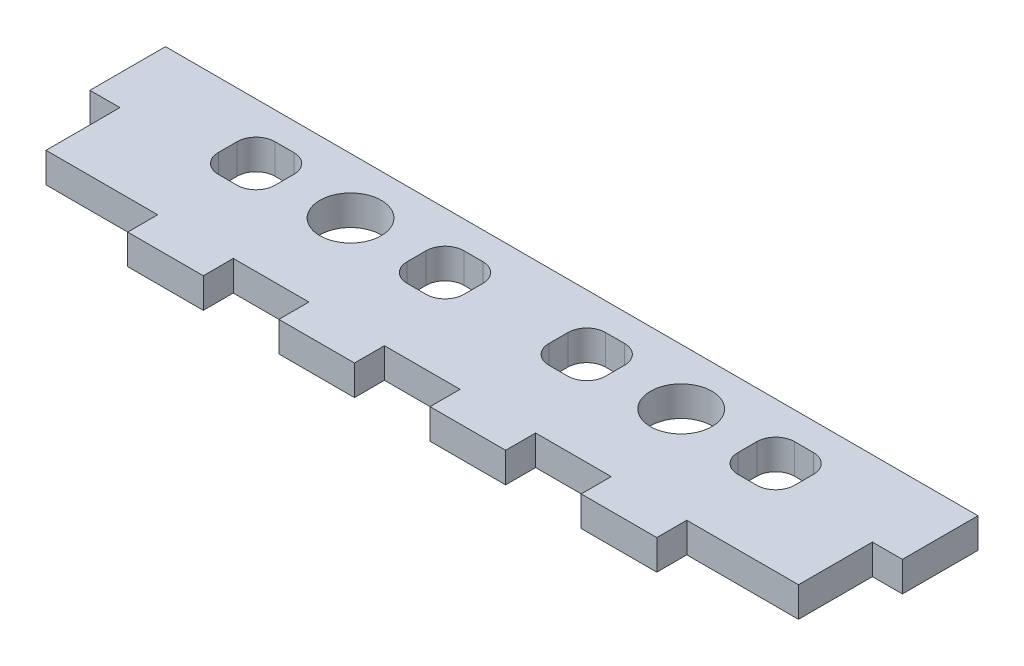
SolidWorks part; units mm, degrees
ref_plane "Front Plane" through (0, 0, 0) normal (0, 0, 1) x (1, 0, 0)
ref_plane "Top Plane" through (0, 0, 0) normal (0, 1, 0) x (1, 0, 0)
ref_plane "Right Plane" through (0, 0, 0) normal (1, 0, 0) x (0, 0, -1)
sketch "Sketch3" plane through (0, 0, 0) normal (0, 1, 0) x (1, 0, 0)
  line L1 (0, 0) -> (86, 0)
  line L2 (0, 0) -> (0, -30)
  line L3 (0, -30) -> (86, -30)
  line L4 (86, 0) -> (86, -30)
  dimension "D1" = 30
  dimension "D2" = 86
extrude "Boss-Extrude1" add sketch "Sketch3" along normal blind 3.175
sketch "Sketch4" plane through (0, 3.175, 0) normal (0, 1, 0) x (1, 0, 0)
  line L0 (43, 0) -> (43, -30) construction
  line L1 (86, 0) -> (0, 0) construction
  line L2 (0, -30) -> (86, -30) construction
  line L3 (0, -15) -> (86, -15) construction
  line L4 (0, 0) -> (0, -30) construction
  line L5 (86, -30) -> (86, 0) construction
  line L6 (15, -30) -> (15, -26.825)
  line L7 (39, -30) -> (47, -30)
  line L8 (0, -26.825) -> (15, -26.825)
  line L9 (39, -26.825) -> (47, -26.825)
  line L10 (47, -30) -> (47, -26.825)
  line L11 (55, -30) -> (63, -30)
  line L12 (55, -30) -> (55, -26.825)
  line L13 (55, -26.825) -> (63, -26.825)
  line L14 (63, -30) -> (63, -26.825)
  line L15 (86, -30) -> (71, -30)
  line L16 (86, -30) -> (86, -26.825)
  line L17 (86, -26.825) -> (71, -26.825)
  line L18 (71, -30) -> (71, -26.825)
  line L19 (0, -30) -> (0, -26.825)
  line L20 (0, -30) -> (15, -30)
  line L21 (23, -30) -> (23, -26.825)
  line L22 (31, -26.825) -> (23, -26.825)
  line L23 (31, -30) -> (31, -26.825)
  line L24 (31, -30) -> (23, -30)
  line L25 (39, -30) -> (39, -26.825)
  line L26 (86, -19) -> (86, -26.825)
  line L27 (0, 0) -> (3.175, 0)
  line L28 (0, 0) -> (0, -11)
  line L29 (0, -11) -> (3.175, -11)
  line L30 (3.175, 0) -> (3.175, -11)
  line L31 (82.825, -19) -> (82.825, -26.825)
  line L32 (86, -19) -> (82.825, -19)
  line L33 (82.825, 0) -> (82.825, -11)
  line L34 (86, -11) -> (82.825, -11)
  line L35 (0, -19) -> (3.175, -19)
  line L36 (0, -19) -> (0, -26.825)
  line L37 (0, -26.825) -> (3.175, -26.825)
  line L38 (3.175, -19) -> (3.175, -26.825)
  line L39 (86, 0) -> (86, -11)
  line L40 (86, 0) -> (82.825, 0)
  line L41 (82.825, -26.825) -> (86, -26.825)
  line L42 (86, -19) -> (86, -26.825)
  point P34 (43, -26.825)
  line M11 (0, 0) -> (0, -30)
  line M12 (0, -30) -> (86, -30)
  line M13 (86, -30) -> (86, 0)
  line M14 (86, 0) -> (0, 0)
  dimension "D1" = 4
  dimension "D2" = 3.175
  dimension "D3" = 8
  dimension "D4" = 3.175
  dimension "D5" = 8
  dimension "D6" = 3.175
  dimension "D7" = 8
  dimension "D8" = 8
extrude "Cut-Extrude1" cut sketch "Sketch4" against normal up to next contours L38 L35 L8 M11 | L8 L6 M11 M12 | L23 L22 L21 M12 | L25 L10 L9 M12 | L14 L13 L12 M12 | L32 L31 L17 M13 | L34 L33 M13 M14 | L18 L17 M12 M13 | L30 L29 M14 M11 | L17 L18 L15 L16 region at (7.5, 3.175, 28.4125) region at (27, 3.175, 28.4125) region at (1.5875, 3.175, 22.9125) region at (43, 3.175, 28.4125) region at (1.5875, 3.175, 5.5) region at (59, 3.175, 28.4125) region at (84.4125, 3.175, 5.5) region at (78.5, 3.175, 28.4125) region at (84.4125, 3.175, 22.9125)
sketch "Sketch5" plane through (0, 3.175, 0) normal (0, 1, 0) x (1, 0, 0)
  line L0 (0, -16.915) -> (86, -16.915) construction
  line L1 (0, -11) -> (0, -19) construction
  line L2 (86, -19) -> (86, -11) construction
  line L3 (31, -26.825) -> (23, -26.825) construction
  line L4 (43, 0) -> (43, -26.825) construction
  line L5 (82.825, 0) -> (3.175, 0) construction
  line L6 (39, -26.825) -> (47, -26.825) construction
  circle A0 centre (60.5, -16.915) radius 3.25
  circle A1 centre (25.5, -16.915) radius 3.25
  point P16 (43, -16.915)
  dimension "D2" = 6.5
  dimension "D1" = 9.91
  dimension "D3" = 17.5
extrude "Cut-Extrude2" cut sketch "Sketch5" against normal up to next
sketch "Sketch6" plane through (0, 3.175, 0) normal (0, 1, 0) x (1, 0, 0)
  line L1 (3.175, -11) -> (82.825, -11)
  line L2 (3.175, -11) -> (3.175, 0)
  line L3 (3.175, 0) -> (82.825, 0)
  line L4 (82.825, -11) -> (82.825, 0)
extrude "Cut-Extrude3" cut sketch "Sketch6" against normal up to next
sketch "Sketch7" plane through (0, 3.175, 0) normal (0, 1, 0) x (1, 0, 0)
  line L0 (43, -11) -> (43, -26.825) construction
  line L1 (86, -11) -> (0, -11) construction
  line L2 (39, -26.825) -> (47, -26.825) construction
  line L3 (22.25, -16.915) -> (63.75, -16.915) construction
  line L4 (14.5, -13.915) -> (16.5, -13.915)
  line L5 (12.5, -15.915) -> (12.5, -17.915)
  line L6 (14.5, -19.915) -> (16.5, -19.915)
  line L7 (18.5, -15.915) -> (18.5, -17.915)
  line L8 (25.5, -13.665) -> (25.5, -20.165) construction
  line L9 (32.5, -15.915) -> (32.5, -17.915)
  line L10 (36.5, -19.915) -> (34.5, -19.915)
  line L11 (38.5, -15.915) -> (38.5, -17.915)
  line L12 (36.5, -13.915) -> (34.5, -13.915)
  line L13 (60.5, -13.665) -> (60.5, -20.165) construction
  line L14 (49.5, -13.915) -> (51.5, -13.915)
  line L15 (47.5, -15.915) -> (47.5, -17.915)
  line L16 (49.5, -19.915) -> (51.5, -19.915)
  line L17 (53.5, -15.915) -> (53.5, -17.915)
  line L18 (67.5, -15.915) -> (67.5, -17.915)
  line L19 (71.5, -19.915) -> (69.5, -19.915)
  line L20 (73.5, -15.915) -> (73.5, -17.915)
  line L21 (71.5, -13.915) -> (69.5, -13.915)
  circle A0 centre (25.5, -16.915) radius 3.25 construction
  circle A1 centre (60.5, -16.915) radius 3.25 construction
  arc A2 (67.5, -17.915) -> (69.5, -19.915) centre (69.5, -17.915) ccw
  arc A3 (71.5, -19.915) -> (73.5, -17.915) centre (71.5, -17.915) ccw
  arc A4 (73.5, -15.915) -> (71.5, -13.915) centre (71.5, -15.915) ccw
  arc A5 (69.5, -13.915) -> (67.5, -15.915) centre (69.5, -15.915) ccw
  arc A6 (47.5, -17.915) -> (49.5, -19.915) centre (49.5, -17.915) ccw
  arc A7 (51.5, -19.915) -> (53.5, -17.915) centre (51.5, -17.915) ccw
  arc A8 (53.5, -15.915) -> (51.5, -13.915) centre (51.5, -15.915) ccw
  arc A9 (49.5, -13.915) -> (47.5, -15.915) centre (49.5, -15.915) ccw
  arc A10 (36.5, -19.915) -> (38.5, -17.915) centre (36.5, -17.915) ccw
  arc A11 (34.5, -19.915) -> (32.5, -17.915) centre (34.5, -17.915) cw
  arc A12 (36.5, -13.915) -> (38.5, -15.915) centre (36.5, -15.915) cw
  arc A13 (34.5, -13.915) -> (32.5, -15.915) centre (34.5, -15.915) ccw
  arc A14 (16.5, -19.915) -> (18.5, -17.915) centre (16.5, -17.915) ccw
  arc A15 (14.5, -19.915) -> (12.5, -17.915) centre (14.5, -17.915) cw
  arc A16 (12.5, -15.915) -> (14.5, -13.915) centre (14.5, -15.915) cw
  arc A17 (18.5, -15.915) -> (16.5, -13.915) centre (16.5, -15.915) ccw
  point P17 (18.5, -16.915)
  point P36 (67.5, -19.915)
  point P39 (73.5, -19.915)
  point P42 (73.5, -13.915)
  point P45 (67.5, -13.915)
  point P48 (47.5, -19.915)
  point P51 (53.5, -19.915)
  point P54 (53.5, -13.915)
  point P57 (47.5, -13.915)
  point P60 (38.5, -19.915)
  point P63 (32.5, -19.915)
  point P66 (38.5, -13.915)
  point P69 (32.5, -13.915)
  point P72 (18.5, -19.915)
  point P75 (12.5, -19.915)
  point P78 (12.5, -13.915)
  point P81 (18.5, -13.915)
  dimension "D5" = 2
  dimension "D1" = 6
  dimension "D2" = 6
  dimension "D3" = 0
  dimension "D4" = 7
extrude "Cut-Extrude4" cut sketch "Sketch7" against normal up to next
